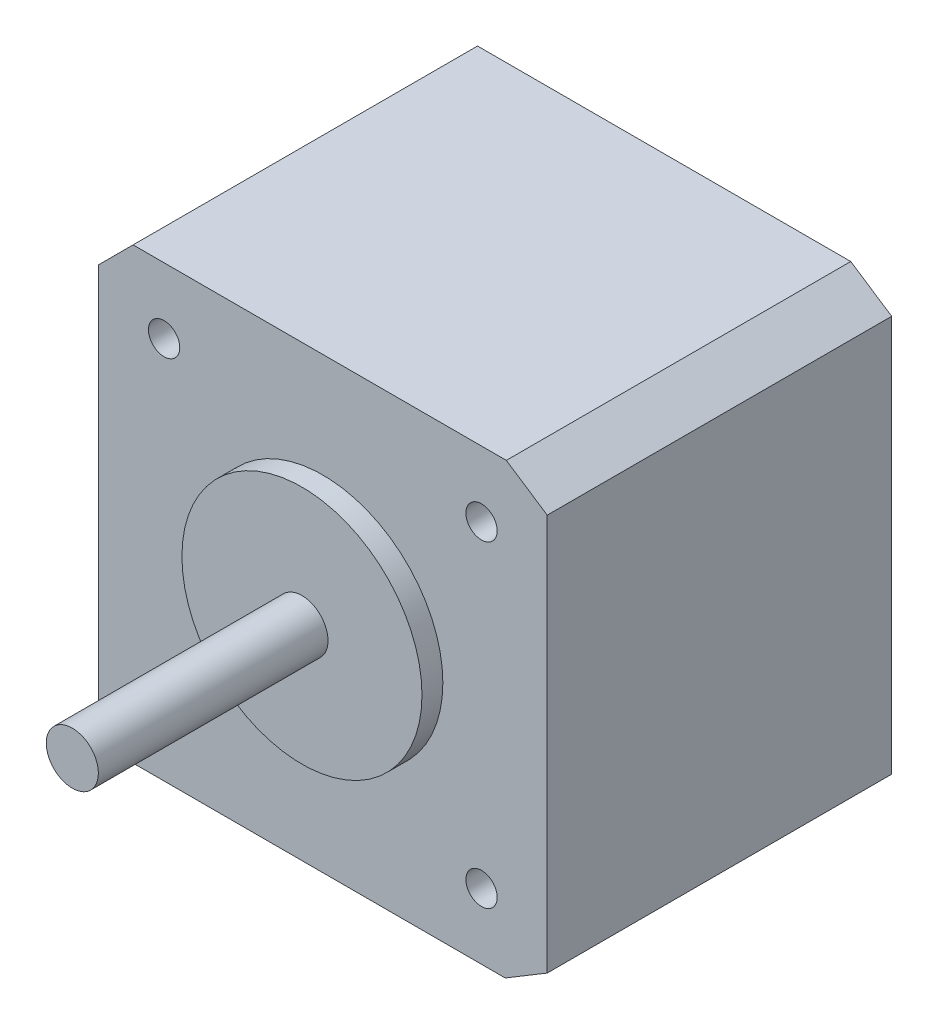
SolidWorks part; units mm, degrees
ref_plane "Front Plane" through (0, 0, 0) normal (0, 0, 1) x (1, 0, 0)
ref_plane "Top Plane" through (0, 0, 0) normal (0, 1, 0) x (1, 0, 0)
ref_plane "Right Plane" through (0, 0, 0) normal (1, 0, 0) x (0, 0, -1)
sketch "Sketch1" plane through (0, 0, 0) normal (0, 0, 1) x (1, 0, 0)
  line L0 (-18.5054, 18.1792) -> (-15.1847, 21.5)
  line L1 (-18.5054, 21.5) -> (24.4946, 21.5)
  line L2 (-18.5054, 21.5) -> (-18.5054, -21.5)
  line L3 (-18.5054, -21.5) -> (24.4946, -21.5)
  line L4 (24.4946, 21.5) -> (24.4946, -21.5)
  line L5 (-18.5054, 21.5) -> (24.4946, -21.5) construction
  line L6 (-18.5054, -21.5) -> (24.4946, 21.5) construction
  line L7 (20.5734, 21.5) -> (24.4946, 18.9156)
  line L8 (-18.5054, -18.1792) -> (-15.1847, -21.5)
  line L9 (20.4702, -21.5) -> (24.4946, -19.0795)
  line L11 (-18.5054, 8.0376) -> (-23.9363, 8.0376)
  line L12 (-18.5054, 8.0376) -> (-18.5054, -7.9631)
  line L13 (-18.5054, -7.9631) -> (-23.9363, -7.9631)
  line L14 (-23.9363, 8.0376) -> (-23.9363, -7.9631)
  line L15 (-18.5054, 8.0376) -> (-23.9363, -7.9631) construction
  line L16 (-18.5054, -7.9631) -> (-23.9363, 8.0376) construction
  circle A0 centre (2.9946, 0) radius 2.4955
  circle A1 centre (2.9946, 0) radius 11.5
  circle A2 centre (-12.2112, 15.2058) radius 1.5
  circle A3 centre (18.2004, 15.2058) radius 1.5
  circle A4 centre (18.2004, -15.2058) radius 1.5
  circle A5 centre (-12.2112, -15.2058) radius 1.5
  point P4 (2.9946, 0)
  point P28 (-21.2209, 0.0372)
  point P29 (0, 0)
  point P30 (0, 0)
  point P31 (0, 0)
  point P32 (0, 0)
  point P33 (0, 0)
  point P34 (-12.1815, -15.176)
  point P35 (-12.2112, -15.2058)
  point P36 (-18.5054, -18.8039)
  dimension "D2" = 23
  dimension "D3" = 3
  dimension "D1" = 43
  dimension "D4" = 45
extrude "Boss-Extrude1" add sketch "Sketch1" along normal blind 33 contours L3 L9 L4 L7 L1 L0 L2 L8 A5 A4 A3 A2 A1 | A1 A0 | A0 region at (-16.415, 19.4096, 0) region at (2.9946, 0, 0) region at (-8.1801, 0, 0)
extrude "Boss-Extrude2" add sketch "Sketch1<3>" along normal blind 35 contours A1
sketch "Sketch1<3>" plane through (0, 0, 0) normal (0, 0, 1) x (1, 0, 0) same geometry as "Sketch1"
extrude "Boss-Extrude3" add sketch "Sketch1<4>" along normal blind 57 contours A0
sketch "Sketch1<4>" plane through (0, 0, 0) normal (0, 0, 1) x (1, 0, 0) same geometry as "Sketch1"
extrude "Boss-Extrude4" add sketch "Sketch1<5>" along normal blind 7 contours L13 L14 L11 L12
sketch "Sketch1<5>" plane through (0, 0, 0) normal (0, 0, 1) x (1, 0, 0) same geometry as "Sketch1"
